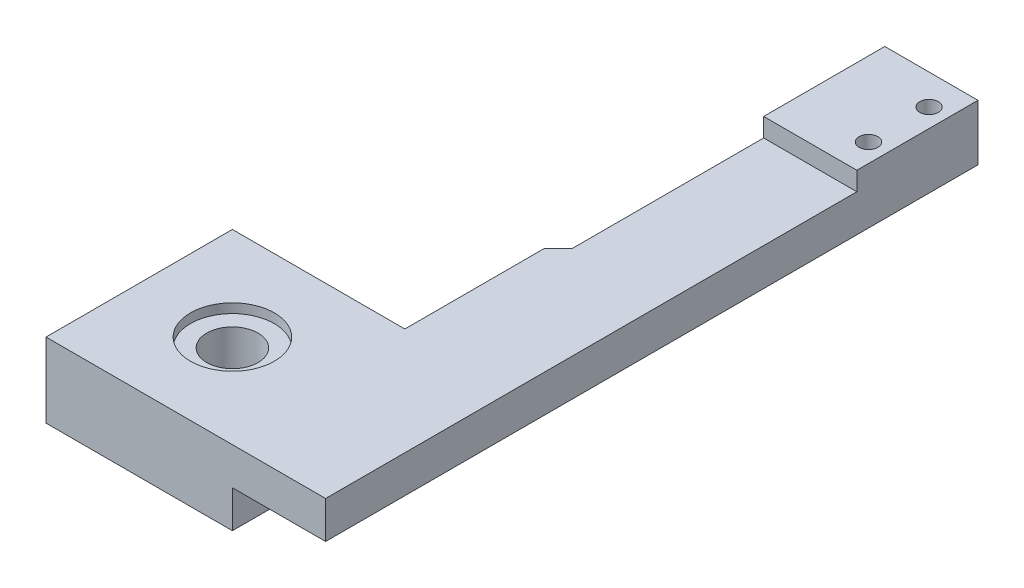
SolidWorks part; units mm, degrees
ref_plane "Front Plane" through (0, 0, 0) normal (0, 0, 1) x (1, 0, 0)
ref_plane "Top Plane" through (0, 0, 0) normal (0, 1, 0) x (1, 0, 0)
ref_plane "Right Plane" through (0, 0, 0) normal (1, 0, 0) x (0, 0, -1)
sketch "Sketch1" plane through (0, 0, 0) normal (0, 1, 0) x (1, 0, 0)
  line L1 (0, 0) -> (30, 0)
  line L2 (0, 0) -> (0, 20)
  line L3 (0, 20) -> (30, 20)
  line L4 (30, 0) -> (30, 20)
  dimension "D1" = 20
  dimension "D2" = 30
extrude "Boss-Extrude1" add sketch "Sketch1" along normal blind 4
sketch "Sketch2" plane through (0, 0, 0) normal (0, -1, 0) x (1, 0, 0)
  line L0 (30, -20) -> (0, -20) construction
  line L1 (0, 0) -> (20, 0)
  line L2 (0, 0) -> (0, -20)
  line L3 (0, -20) -> (20, -20)
  line L4 (20, 0) -> (20, -20)
  dimension "D1" = 20
extrude "Boss-Extrude2" add sketch "Sketch2" along normal blind 4
sketch "Sketch3" plane through (0, 4, 0) normal (0, 1, 0) x (1, 0, 0)
  line L0 (0, 20) -> (20, 0) construction
  line L1 (0, 0) -> (30, 0) construction
  line L2 (0, 0) -> (20, 20) construction
  line L3 (30, 20) -> (0, 20) construction
  point P10 (10, 10)
hole_wizard "CBORE for M5 SBHCS1" positions "Sketch8" profile "Sketch9" counterbore size "M5" standard "ANSI Metric" end condition through all
sketch "Sketch8" plane through (0, 4, 0) normal (0, 1, 0) x (1, 0, 0)
  point P0 (10, 10)
sketch "Sketch9" plane through (10, 4, -10) normal (1, 0, 0) x (0, 0, 1)
  line L0 (0, 0) -> (0, 8)
  line L1 (0, 8) -> (2.75, 8)
  line L3 (2.75, 8) -> (2.75, 1)
  line L4 (2.75, 1) -> (4.5, 1)
  line L5 (4.5, 1) -> (4.5, 0)
  line L7 (4.5, 0) -> (0, 0)
  line L11 (0, -6.35) -> (0, 107.95) construction
  dimension "Thru Hole Dia." = 5.5
  dimension "Thru Hole Depth" = 8
  dimension "C'Bore Dia." = 9
  dimension "C'Bore Depth" = 1
sketch "Sketch10" plane through (0, 0, -20) normal (0, 0, -1) x (-1, 0, 0)
  line L1 (-30, 4) -> (-20, 4)
  line L2 (-30, 4) -> (-30, 0)
  line L3 (-30, 0) -> (-20, 0)
  line L4 (-20, 4) -> (-20, 0)
  line L5 (-20, 4) -> (-18.5, 4)
  line L6 (-20, 4) -> (-20, -1.5)
  line L7 (-20, -1.5) -> (-18.5, -1.5)
  line L8 (-18.5, 4) -> (-18.5, -1.5)
  line M2 (-30, 0) -> (-20, 0)
  line M3 (-20, 0) -> (-20, -4)
  line M6 (0, 4) -> (-30, 4)
  line M7 (-30, 4) -> (-30, 0)
  dimension "D1" = 1.5
  dimension "D2" = 5.5
extrude "Boss-Extrude3" add sketch "Sketch10" along normal blind 50 contours L4 M6 M7 M2 region at (25, 2, -20)
extrude "Boss-Extrude4" add sketch "Sketch10<3>" along normal blind 15 contours L8 L4 L7 M6 M3 region at (19.25, 1.25, -20)
sketch "Sketch10<3>" plane through (0, 0, -20) normal (0, 0, -1) x (-1, 0, 0) same geometry as "Sketch10"
sketch "Sketch11" plane through (0, 4, 0) normal (0, 1, 0) x (1, 0, 0)
  line L0 (20, 70) -> (20, 35) construction
  line L1 (30, 70) -> (20, 70)
  line L2 (30, 70) -> (30, 57)
  line L3 (30, 57) -> (20, 57)
  line L4 (20, 70) -> (20, 57)
  dimension "D1" = 13
extrude "Boss-Extrude5" add sketch "Sketch11" along normal blind 2
sketch "Sketch12" plane through (0, 6, 0) normal (0, 1, 0) x (1, 0, 0)
  line L0 (28, 57) -> (28, 70) construction
  line L1 (20, 57) -> (30, 57) construction
  line L2 (30, 70) -> (20, 70) construction
  line L3 (30, 57) -> (30, 70) construction
  circle A0 centre (28, 60.25) radius 1
  circle A1 centre (28, 66.75) radius 1
  point P6 (28, 60.25)
  point P7 (28, 66.75)
  point P8 (28, 63.5)
  dimension "D4" = 2
  dimension "D1" = 6.5
  dimension "D2" = 3.25
  dimension "D3" = 2
ref_plane "Plane2" through (-10, 0, 0) normal (-1, 0, 0) x (0, 0, 1)
extrude "Cut-Extrude1" cut sketch "Sketch12" against normal blind 4
chamfer "Chamfer1" distance 1.5 angle 45 1 edges at (20, 2, -35)
